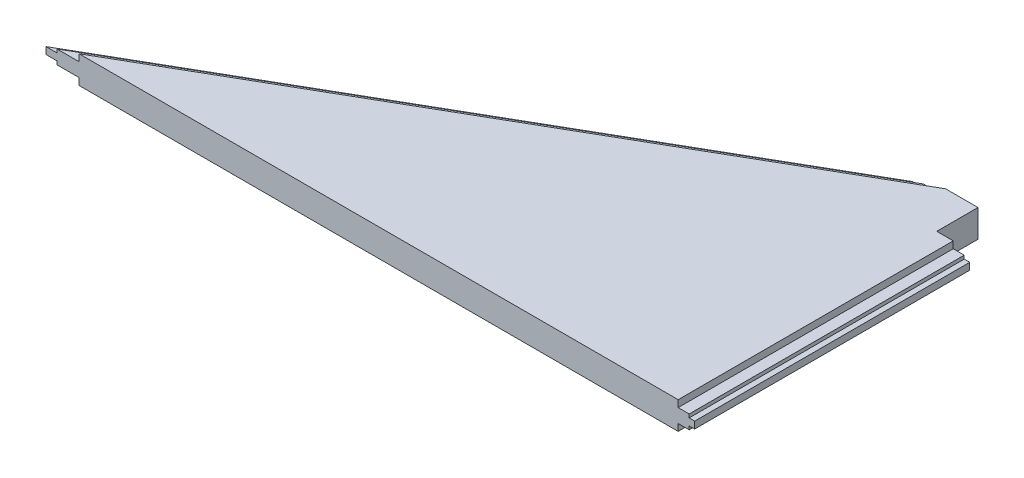
SolidWorks part; units mm, degrees
ref_plane "Front Plane" through (0, 0, 0) normal (0, 0, 1) x (1, 0, 0)
ref_plane "Top Plane" through (0, 0, 0) normal (0, 1, 0) x (1, 0, 0)
ref_plane "Right Plane" through (0, 0, 0) normal (1, 0, 0) x (0, 0, -1)
sketch "Sketch1" plane through (0, 0, 0) normal (0, 1, 0) x (1, 0, 0)
  line L0 (-406.4, 0) -> (0, 0)
  line L1 (0, 0) -> (0, 146.05)
  line L2 (0, 146.05) -> (-152.4, 146.05)
  line L3 (-152.4, 146.05) -> (-406.4, 0)
  dimension "D1" = 406.4
  dimension "D2" = 152.4
  dimension "D3" = 146.05
extrude "Boss-Extrude1" add sketch "Sketch1" along normal blind 6.35 and the other way blind 6.35 contours L3 L0 L1 L2
sketch "Sketch2" plane through (-100.9796, 0, -175.6167) normal (-0.4985, 0, -0.8669) x (-0.8669, 0, 0.4985)
  line L0 (59.3148, 6.35) -> (59.3148, 3.175)
  line L1 (59.3148, -6.35) -> (59.3148, 6.35) construction
  line L2 (59.3148, 3.175) -> (352.3107, 3.175)
  line L3 (352.3107, -6.35) -> (352.3107, 6.35) construction
  line L4 (352.3107, 3.175) -> (352.3107, 6.35)
  line L5 (352.3107, 6.35) -> (59.3148, 6.35)
  line L6 (59.3148, -6.35) -> (59.3148, -3.175)
  line L7 (59.3148, -6.35) -> (352.3107, -6.35)
  line L8 (352.3107, -6.35) -> (352.3107, -3.175)
  line L9 (352.3107, -3.175) -> (59.3148, -3.175)
  dimension "D1" = 3.175
  dimension "D2" = 3.175
extrude "Cut-Extrude1" cut sketch "Sketch2" against normal blind 38.1
sketch "Sketch3" plane through (0, 0, 0) normal (1, 0, 0) x (0, 0, -1)
  line L0 (0, 6.35) -> (0, 3.175)
  line L2 (0, 6.35) -> (146.05, 6.35)
  line L3 (146.05, 6.35) -> (146.05, 3.175)
  line L4 (146.05, -6.35) -> (146.05, 6.35) construction
  line L5 (0, 3.175) -> (146.05, 3.175)
  line L6 (0, -6.35) -> (0, -3.175)
  line L7 (0, -3.175) -> (146.05, -3.175)
  line L8 (146.05, -3.175) -> (146.05, -6.35)
  line L9 (146.05, -6.35) -> (0, -6.35)
  dimension "D1" = 3.175
  dimension "D2" = 3.175
  dimension "D3" = 3.175
  dimension "D4" = 3.175
extrude "Cut-Extrude2" cut sketch "Sketch3" against normal blind 38.1
sketch "Sketch4" plane through (0, 6.35, 0) normal (0, 1, 0) x (1, 0, 0)
  line L0 (-133.4083, 113.0209) -> (-75.9663, 146.05)
  line L1 (-38.1, 146.05) -> (-152.4, 146.05) construction
  line L2 (-75.9663, 146.05) -> (-152.4, 146.05)
  line L3 (-152.4, 146.05) -> (-133.4083, 113.0209)
  line L4 (-329.9663, 0) -> (-133.4083, 113.0209) construction
extrude "Cut-Extrude3" cut sketch "Sketch4" against normal blind 3.175
sketch "Sketch5" plane through (0, -6.35, 0) normal (0, -1, 0) x (1, 0, 0)
  line L0 (-133.4083, -113.0209) -> (-75.9663, -146.05)
  line L1 (-38.1, -146.05) -> (-152.4, -146.05) construction
  line L2 (-75.9663, -146.05) -> (-152.4, -146.05)
  line L3 (-152.4, -146.05) -> (-133.4083, -113.0209)
  line L4 (-329.9663, 0) -> (-133.4083, -113.0209) construction
extrude "Cut-Extrude4" cut sketch "Sketch5" against normal blind 3.175
sketch "Sketch6" plane through (0, 0, -146.05) normal (0, 0, -1) x (-1, 0, 0)
  line L0 (38.1, 6.35) -> (0, 0) construction
  line L1 (0, 0) -> (38.1, -6.35) construction
  line L2 (0, -3.175) -> (0, 3.175) construction
  line L3 (38.622, 3.2182) -> (19.3128, 0) construction
  line L4 (19.3128, 0) -> (38.622, -3.2182) construction
  line L5 (38.1, -3.175) -> (43.18, -3.175)
  line L6 (43.18, -3.175) -> (43.18, -6.35)
  line L7 (38.1, -6.35) -> (75.9663, -6.35) construction
  line L8 (43.18, -6.35) -> (38.1, -6.35)
  line L9 (38.1, 3.175) -> (43.18, 3.175)
  line L10 (43.18, 3.175) -> (43.18, 6.35)
  line L11 (38.1, 6.35) -> (75.9663, 6.35) construction
  line L12 (43.18, 6.35) -> (38.1, 6.35)
  line L13 (38.1, 6.35) -> (0, 6.35)
  line L14 (0, 6.35) -> (0, -6.35)
  line L15 (0, -6.35) -> (38.1, -6.35)
  line L16 (38.1, -3.175) -> (38.1, -1.5875)
  line L22 (38.1, -1.5875) -> (35.56, -1.5875)
  line L23 (35.56, -1.5875) -> (35.56, 1.5875)
  line L24 (35.56, 1.5875) -> (38.1, 1.5875)
  line L25 (38.1, 1.5875) -> (38.1, 3.175)
  line M7 (75.9663, 6.35) -> (38.1, 6.35)
  line M8 (38.1, 6.35) -> (38.1, 3.175)
  line M9 (38.1, 3.175) -> (0, 3.175)
  line M10 (0, 3.175) -> (0, -3.175)
  line M11 (0, -3.175) -> (38.1, -3.175)
  line M12 (38.1, -3.175) -> (38.1, -6.35)
  line M13 (38.1, -6.35) -> (75.9663, -6.35)
  dimension "D2" = 1.5875
  dimension "D1" = 3.175
  dimension "D3" = 5.08
  dimension "D4" = 5.08
  dimension "D5" = 2.54
  dimension "D6" = 3.175
extrude "Cut-Extrude5" cut sketch "Sketch6" against normal blind 157.099 contours L9 L10 M7 M8 | L6 L5 M12 M13 | L4 L3 M11 M9 M10 | L4 L3 region at (-18.4369, 0, -146.05) region at (-40.64, -4.7625, -146.05) region at (-40.64, 4.7625, -146.05)
sketch "Sketch7" plane through (0, -3.175, 0) normal (0, -1, 0) x (1, 0, 0)
  line L0 (-152.4, -146.05) -> (-133.4083, -113.0209) construction
  line L1 (-329.9663, 0) -> (-75.9663, -146.05) construction
  line L2 (-75.9663, -146.05) -> (-329.9663, 0) construction
ref_plane "Plane1" through (-51.4204, 0, 29.5667) normal (-0.8669, 0, 0.4985) x (0.4985, 0, 0.8669)
sketch "Sketch8" plane through (-51.4204, 0, 29.5667) normal (-0.8669, 0, 0.4985) x (0.4985, 0, 0.8669)
  line L0 (-202.5787, 0) -> (-164.4787, 0) construction
  line L1 (-202.5787, -3.175) -> (-202.5787, 3.175) construction
  line L2 (-164.4787, 0) -> (-164.4787, -6.35) construction
  line L3 (-164.4787, -6.35) -> (-202.5787, 0) construction
  line L4 (-202.5787, 0) -> (-164.4787, 6.35) construction
  line L5 (-164.4787, 0) -> (-164.4787, 6.35) construction
  line L6 (-163.9567, -3.2182) -> (-183.2659, 0) construction
  line L7 (-183.2659, 0) -> (-163.9567, 3.2182) construction
  line L8 (-164.4787, 3.175) -> (-159.3987, 3.175)
  line L9 (-159.3987, 3.175) -> (-159.3987, 6.35)
  line L10 (-159.3987, 6.35) -> (-164.4787, 6.35)
  line L11 (-164.4787, -3.175) -> (-159.3987, -3.175)
  line L12 (-159.3987, -3.175) -> (-159.3987, -6.35)
  line L13 (-159.3987, -6.35) -> (-164.4787, -6.35)
  line L14 (-164.4787, 6.35) -> (-202.5787, 6.35)
  line L15 (-202.5787, 6.35) -> (-202.5787, -6.35)
  line L16 (-202.5787, -6.35) -> (-164.4787, -6.35)
  line L17 (-164.4787, -3.175) -> (-164.4787, -1.5875)
  line L18 (-164.4787, -1.5875) -> (-167.0187, -1.5875)
  line L19 (-167.0187, -1.5875) -> (-167.0187, 1.5875)
  line L20 (-167.0187, 1.5875) -> (-164.4787, 1.5875)
  line L21 (-164.4787, 1.5875) -> (-164.4787, 3.175)
  point P7 (-164.4787, -3.175)
  point P11 (-164.4787, 3.175)
  dimension "D5" = 1.5875
  dimension "D1" = 38.1
  dimension "D2" = 6.35
  dimension "D3" = 6.35
  dimension "D6" = 5.08
  dimension "D7" = 3.175
  dimension "D8" = 5.08
  dimension "D9" = 3.175
  dimension "D10" = 38.1
  dimension "D11" = 12.7
  dimension "D12" = 2.54
  dimension "D13" = 3.175
  dimension "D14" = 1.5875
  dimension "D4" = 3.175
extrude "Cut-Extrude6" cut sketch "Sketch8" against normal blind 157.099 and the other way blind 339.217 contours L8 L9 L10 L14 L15 L16 L13 L12 L11 L6 L7 | L7 L6 | L17 L6 | L7 region at (-142.3615, 0, -128.5917)
sketch "Sketch9" plane through (0, 6.35, 0) normal (0, 1, 0) x (1, 0, 0)
  line L5 (0, 146.05) -> (-50.8, 146.05)
  line L6 (0, 146.05) -> (-152.4, 146.05) construction
  line L7 (-50.8, 146.05) -> (-50.8, 127)
  line L8 (-50.8, 127) -> (0, 127)
  line L9 (0, 0) -> (0, 146.05) construction
  line L10 (0, 146.05) -> (0, 127)
  dimension "D1" = 50.8
  dimension "D2" = 19.05
extrude "Cut-Extrude7" cut sketch "Sketch9" against normal blind 21.59
